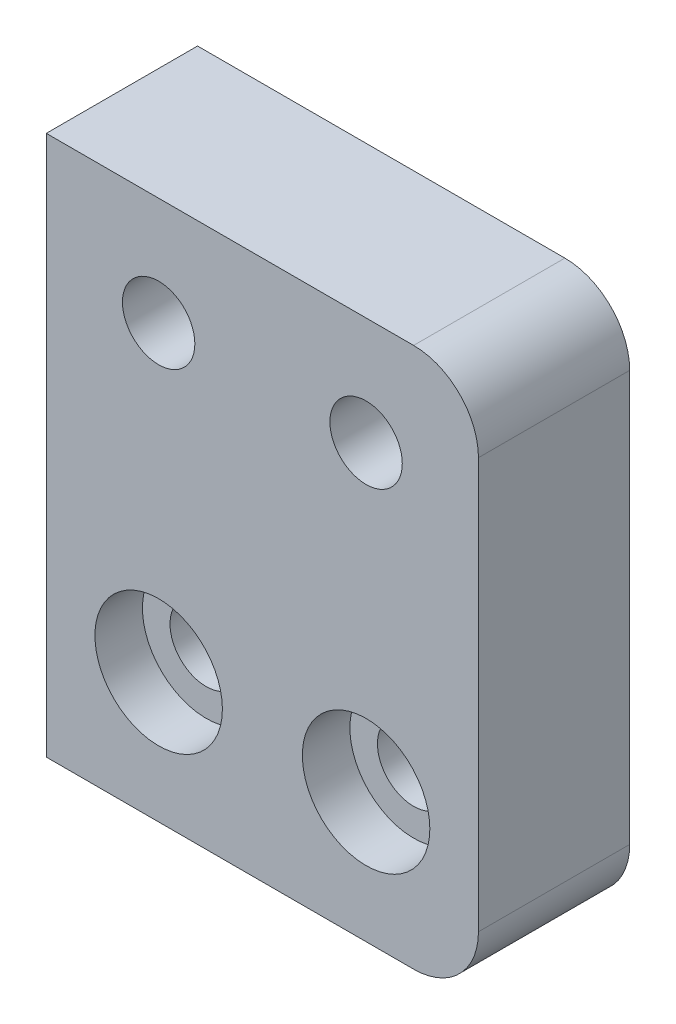
SolidWorks part; units mm, degrees
material "ABS"
ref_plane "Front Plane" through (0, 0, 0) normal (0, 0, 1) x (1, 0, 0)
ref_plane "Top Plane" through (0, 0, 0) normal (0, 1, 0) x (1, 0, 0)
ref_plane "Right Plane" through (0, 0, 0) normal (1, 0, 0) x (0, 0, -1)
sketch "Sketch1" plane through (0, 0, 0) normal (0, 0, 1) x (1, 0, 0)
  line L0 (0, 14) -> (20, 14) construction
  line L1 (0, 0) -> (17, 0)
  line L2 (0, 0) -> (0, 25)
  line L3 (0, 25) -> (17, 25)
  line L4 (20, 3) -> (20, 22)
  line L5 (10, 25) -> (10, 0) construction
  line L6 (5.2, 20) -> (14.8, 20) construction
  arc A0 (17, 0) -> (20, 3) centre (17, 3) ccw
  arc A1 (20, 22) -> (17, 25) centre (17, 22) ccw
  circle A2 centre (5.2, 20) radius 1.675
  circle A3 centre (14.8, 20) radius 1.675
  circle A4 centre (5.2, 6) radius 1.675
  circle A5 centre (14.8, 6) radius 1.675
  point P9 (20, 25)
  point P14 (10, 14)
  point P23 (10, 20)
  dimension "D3" = 3
  dimension "D4" = 9.6
  dimension "D5" = 3.35
  dimension "D6" = 6
  dimension "D7" = 3.35
  dimension "D8" = 8
  dimension "D1" = 25
  dimension "D2" = 20
  dimension "D9" = 5
extrude "Boss-Extrude1" add sketch "Sketch1" along normal blind 7
sketch "Sketch2" plane through (0, 0, 7) normal (0, 0, 1) x (1, 0, 0)
  circle A0 centre (5.2, 6) radius 2.95
  circle A1 centre (14.8, 6) radius 2.95
  dimension "D1" = 5.9
extrude "Cut-Extrude1" cut sketch "Sketch2" against normal blind 2.2
sketch "Sketch3" plane through (0, 0, 0) normal (0, 0, -1) x (-1, 0, 0)
  circle A0 centre (-14.8, 20) radius 3
  circle A1 centre (-5.2, 20) radius 3
  dimension "D1" = 6
extrude "Cut-Extrude2" cut sketch "Sketch3" against normal blind 2
